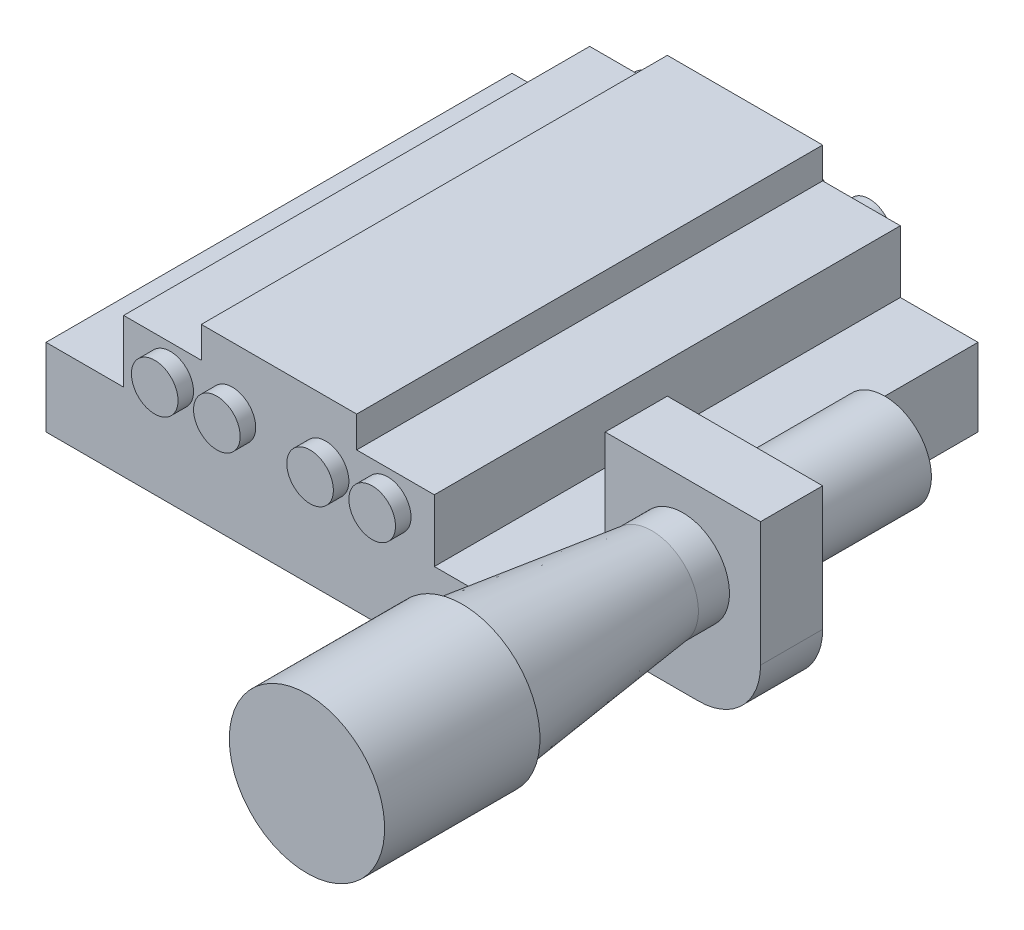
SolidWorks part; units mm, degrees
material "Простая углеродистая сталь"
ref_plane "Спереди" through (0, 0, 0) normal (0, 0, 1) x (1, 0, 0)
ref_plane "Сверху" through (0, 0, 0) normal (0, 1, 0) x (1, 0, 0)
ref_plane "Справа" through (0, 0, 0) normal (1, 0, 0) x (0, 0, -1)
sketch "Эскиз2" plane through (0, 0, 0) normal (0, 1, 0) x (1, 0, 0)
  line L0 (0, 0) -> (30, 0)
  line L1 (0, 0) -> (0, 30)
  line L2 (30, 0) -> (30, 30)
  line L3 (0, 30) -> (30, 30)
  dimension "D1" = 30
  dimension "D2" = 30
extrude "Бобышка-Вытянуть1" add sketch "Эскиз2" along normal blind 5
sketch "Эскиз3" plane through (0, 0, 0) normal (0, -1, 0) x (1, 0, 0)
  line L0 (27, -3) -> (27, -27) construction
  line L1 (27, -3) -> (3, -3) construction
  line L2 (27, -27) -> (3, -27) construction
  line L3 (3, -3) -> (3, -27) construction
  line L4 (30, -15) -> (0, -15) construction
  line L5 (30, 0) -> (30, -30) construction
  line L6 (0, -30) -> (0, 0) construction
  line L7 (15, 0) -> (15, -30) construction
  line L8 (0, 0) -> (30, 0) construction
  line L9 (30, -30) -> (0, -30) construction
  circle A0 centre (27, -3) radius 1
  circle A1 centre (27, -27) radius 1
  circle A2 centre (3, -27) radius 1
  circle A3 centre (3, -3) radius 1
  point P16 (27, -15)
  point P17 (15, -3)
  dimension "D3" = 2
  dimension "D1" = 24
  dimension "D2" = 24
extrude "Вырез-Вытянуть1" cut sketch "Эскиз3" against normal blind 3
sketch "Эскиз5" plane through (0, 0, 0) normal (0, 0, 1) x (1, 0, 0)
  line L0 (5, 9) -> (5, 5) construction
  line L1 (10, 9) -> (5, 9) construction
  line L2 (10, 11) -> (10, 9) construction
  line L3 (20, 11) -> (10, 11) construction
  line L4 (20, 9) -> (20, 11) construction
  line L5 (25, 5) -> (25, 9) construction
  line L6 (25, 9) -> (20, 9) construction
  line L7 (5, 9) -> (5, 5)
  line L8 (10, 9) -> (5, 9)
  line L9 (10, 11) -> (10, 9)
  line L10 (20, 11) -> (10, 11)
  line L11 (20, 9) -> (20, 11)
  line L12 (25, 5) -> (25, 9)
  line L13 (25, 9) -> (20, 9)
  line L14 (5, 5) -> (25, 5)
  line L15 (25, 5) -> (24.9899, 5.0574)
extrude "Бобышка-Вытянуть2" add sketch "Эскиз5" against normal up to surface (30 mm away) up to face at (15, 2.5, -30)
sketch "Эскиз6" plane through (30, 0, 0) normal (1, 0, 0) x (0, 0, -1)
  line L0 (0, 4) -> (15, 4)
  line L2 (0, 4) -> (0, 2)
  line L3 (15, 4) -> (15, 2)
  line L4 (0, 2) -> (15, 2)
  line L5 (0, 5) -> (0, 0) construction
  line L6 (0, 5) -> (30, 5) construction
  dimension "D1" = 1
  dimension "D2" = 15
  dimension "D3" = 2
extrude "Бобышка-Вытянуть3" add sketch "Эскиз6" along normal blind 8
sketch "Эскиз7" plane through (0, 4, 0) normal (0, 1, 0) x (1, 0, 0)
  line L0 (32, 4) -> (42, 4)
  line L1 (32, 4) -> (32, 8)
  line L2 (42, 4) -> (42, 8)
  line L3 (32, 8) -> (42, 8)
  line L4 (30, 15) -> (30, 0) construction
  line L5 (38, 0) -> (30, 0) construction
  point P4 (34, 0)
  dimension "D1" = 4
  dimension "D2" = 10
  dimension "D3" = 2
  dimension "D4" = 4
extrude "Бобышка-Вытянуть4" add sketch "Эскиз7" along normal blind 10
sketch "Эскиз8" plane through (0, 0, -4) normal (0, 0, 1) x (1, 0, 0)
  line L0 (37, 14) -> (37, 4) construction
  line L1 (32, 14) -> (42, 14) construction
  line L2 (32, 4) -> (38, 4) construction
  line L3 (42, 9) -> (32, 9) construction
  line L4 (42, 14) -> (42, 4) construction
  line L5 (32, 14) -> (32, 4) construction
ref_plane "Плоскость1" through (37, 0, 0) normal (-1, 0, 0) x (0, 0, 1)
sketch "Эскиз9" plane through (37, 0, 0) normal (-1, 0, 0) x (0, 0, 1)
  line L1 (-4, 9) -> (20.2, 9) construction
  line L2 (-4, 14) -> (-4, 4) construction
  line L3 (20.2, 9) -> (20.2, 14)
  line L4 (20.2, 14) -> (10.2, 14)
  line L5 (10.2, 14) -> (10.2, 13.5)
  line L6 (-2, 12) -> (-17, 12)
  line L7 (-17, 12) -> (-17, 10.5)
  line L8 (-17, 10.5) -> (-18, 10.5)
  line L9 (-18, 10.5) -> (-18, 9)
  line L10 (-18, 9) -> (20.2, 9)
  line L11 (10.2, 13.5) -> (-2, 12)
  line L12 (-8, 14) -> (-8, 4) construction
  line L14 (0, 2) -> (0, 0) construction
  dimension "D1" = 20.2
  dimension "D2" = 0.5
  dimension "D3" = 3
  dimension "D4" = 5
  dimension "D5" = 2
  dimension "D6" = 1.5
  dimension "D7" = 10
  dimension "D8" = 1
  dimension "D9" = 9
revolve "Повернуть1" add sketch "Эскиз9" angle 360 about L1
sketch "Эскиз10" plane through (0, 0, -15) normal (0, 0, -1) x (-1, 0, 0)
  line L4 (-30, 2) -> (-30, 4)
  line L5 (-30, 4) -> (-38, 4)
  line L6 (-38, 4) -> (-38, 2)
  line L7 (-38, 2) -> (-30, 2)
  line L8 (-30, 2) -> (-30, 4)
  line L9 (-30, 4) -> (-38, 4)
  line L10 (-38, 4) -> (-38, 2)
  line L11 (-38, 2) -> (-30, 2)
  dimension "D1" = 0
extrude "Вырез-Вытянуть2" cut sketch "Эскиз10" against normal up to surface (7 mm away) up to face at (40, 9, -8)
sketch "Эскиз11" plane through (0, 0, 0) normal (0, 0, 1) x (1, 0, 0)
  line L0 (38, 4) -> (38, 2) construction
  line L1 (38, 2) -> (30, 2) construction
  line L2 (38, 4) -> (30, 4) construction
  line L3 (38, 4) -> (38, 2)
  line L4 (38, 2) -> (30, 2)
  line L5 (38, 4) -> (30, 4)
  line L6 (30, 4) -> (30, 2)
extrude "Вырез-Вытянуть3" cut sketch "Эскиз11" against normal up to surface (4 mm away) up to face at (34, 9, -4)
sketch "Эскиз12" plane through (38, 0, 0) normal (1, 0, 0) x (0, 0, -1)
  line L4 (4, 4) -> (4, 2)
  line L5 (4, 2) -> (8, 2)
  line L6 (8, 2) -> (8, 4)
  line L7 (8, 4) -> (4, 4)
  line L8 (4, 4) -> (4, 2)
  line L9 (4, 2) -> (8, 2)
  line L10 (8, 2) -> (8, 4)
  line L11 (8, 4) -> (4, 4)
  dimension "D1" = 0
extrude "Бобышка-Вытянуть5" add sketch "Эскиз12" along normal up to surface (4 mm away) up to face at (42, 9, -6)
fillet "Скругление1" radius 4 1 edges at (42, 2, -6)
fillet "Скругление2" radius 2 1 edges at (32, 4, -6)
sketch "Эскиз13" plane through (0, 0, 0) normal (0, 0, 1) x (1, 0, 0)
  line L0 (5, 7) -> (25, 7) construction
  line L1 (5, 9) -> (5, 5) construction
  line L2 (25, 5) -> (25, 9) construction
  line L3 (15, 11) -> (15, 0) construction
  line L4 (20, 11) -> (10, 11) construction
  line L5 (0, 0) -> (30, 0) construction
  circle A0 centre (8, 7) radius 1.5
  circle A1 centre (12, 7) radius 1.5
  circle A2 centre (22, 7) radius 1.5
  circle A3 centre (18, 7) radius 1.5
  dimension "D1" = 3
  dimension "D2" = 4
  dimension "D3" = 3
extrude "Бобышка-Вытянуть6" add sketch "Эскиз13" along normal blind 1
sketch "Эскиз14" plane through (0, 0, -30) normal (0, 0, -1) x (-1, 0, 0)
  circle A0 centre (-8, 7) radius 1.5 construction
  circle A1 centre (-12, 7) radius 1.5 construction
  circle A2 centre (-18, 7) radius 1.5 construction
  circle A3 centre (-22, 7) radius 1.5 construction
  circle A4 centre (-8, 7) radius 1.5
  circle A5 centre (-12, 7) radius 1.5
  circle A6 centre (-18, 7) radius 1.5
  circle A7 centre (-22, 7) radius 1.5
extrude "Бобышка-Вытянуть7" add sketch "Эскиз14" along normal blind 1
